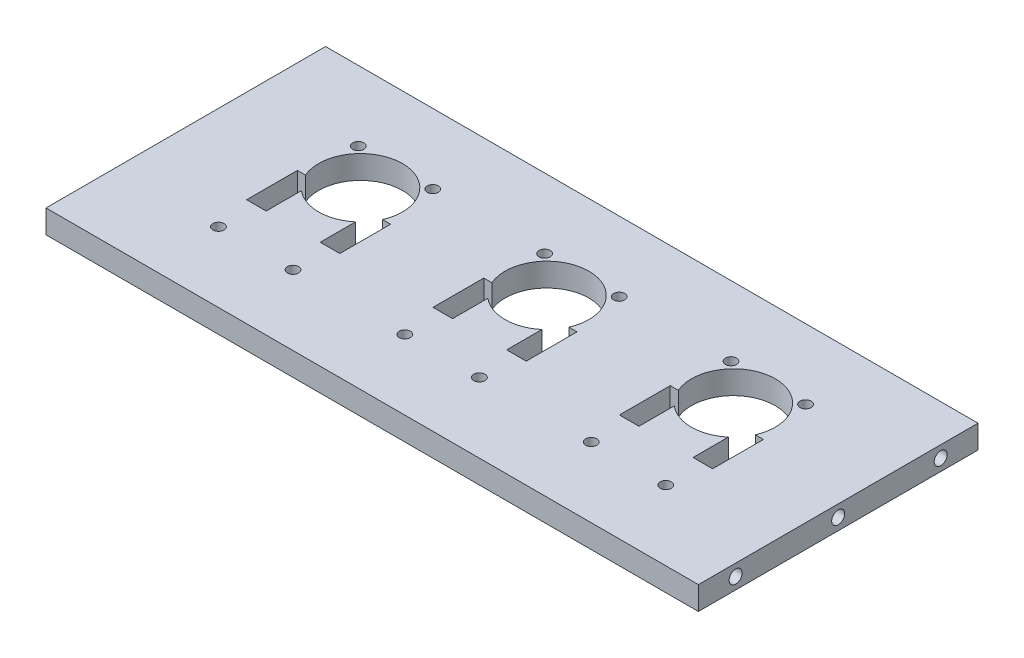
SolidWorks part; units mm, degrees
material "PET"
ref_plane "前视基准面" through (0, 0, 0) normal (0, 0, 1) x (1, 0, 0)
ref_plane "上视基准面" through (0, 0, 0) normal (0, 1, 0) x (1, 0, 0)
ref_plane "右视基准面" through (0, 0, 0) normal (1, 0, 0) x (0, 0, -1)
sketch "草图1" plane through (0, 0, 0) normal (0, 1, 0) x (1, 0, 0)
  line L0 (0, 0) -> (140, 0)
  line L1 (140, 0) -> (140, -60)
  line L2 (140, -60) -> (0, -60)
  line L3 (0, -60) -> (0, 0)
  dimension "D1" = 140
  dimension "D2" = 60
extrude "凸台-拉伸1" add sketch "草图1" along normal blind 5
ref_plane "基准面1" through (0, 0, 30) normal (0, 0, 1) x (1, 0, 0)
sketch "草图2" plane through (0, 5, 0) normal (0, 1, 0) x (1, 0, 0)
  line L0 (140, -30) -> (140, -13) construction
  line L1 (140, -60) -> (140, 0) construction
  line L2 (140, -30) -> (140, -47) construction
  line L3 (0, -13) -> (30, -13) construction
  line L4 (0, 0) -> (0, -60) construction
  line L5 (0, -13) -> (0, -47) construction
  line L6 (0, -47) -> (140, -47) construction
  line L7 (100, -13) -> (120, -13) construction
  line L8 (100, -13) -> (100, -47) construction
  line L9 (120, -13) -> (120, -47) construction
  line L10 (110, -13) -> (110, -15) construction
  line L11 (102, -15) -> (118, -15) construction
  line L12 (-2.75, -30) -> (2.75, -30) construction
  line L13 (100, -13) -> (140, -13) construction
  line L14 (100, -26.05) -> (100, -36.95)
  line L15 (100, -26.05) -> (101.7297, -26.05)
  line L16 (104.2, -29.3819) -> (104.2, -36.95)
  line L17 (104.2, -36.95) -> (100, -36.95)
  line L18 (120, -26.05) -> (118.2703, -26.05)
  line L19 (115.8, -29.3819) -> (115.8, -36.95)
  line L20 (115.8, -36.95) -> (120, -36.95)
  line L21 (120, -36.95) -> (120, -26.05)
  line L22 (110, -31.5) -> (110, -47) construction
  circle A0 centre (102, -15) radius 1.2
  circle A1 centre (118, -15) radius 1.2
  circle A2 centre (102, -45) radius 1.2
  circle A3 centre (118, -45) radius 1.2
  arc A4 (104.2, -29.3819) -> (115.8, -29.3819) centre (110, -22.5) ccw
  arc A5 (118.2703, -26.05) -> (101.7297, -26.05) centre (110, -22.5) ccw
  point P22 (110, -15)
  point P28 (110, -22.5)
  dimension "D12" = 2.4
  dimension "D13" = 2.4
  dimension "D15" = 13.05
  dimension "D1" = 17
  dimension "D2" = 17
  dimension "D3" = 140
  dimension "D4" = 13.05
  dimension "D5" = 10.9
  dimension "D6" = 20
  dimension "D7" = 20
  dimension "D10" = 16
  dimension "D11" = 15
  dimension "D14" = 9.5
  dimension "D16" = 23.95
  dimension "D17" = 10.9
extrude "电机孔位" cut sketch "草图2" against normal through all
ref_plane "基准面2" through (0, 2.5, 0) normal (0, 1, 0) x (1, 0, 0)
ref_axis "基准轴1" through (140, 5, 60) along (0, 0, -1)
ref_axis "基准轴2" through (140, 5, 60) along (0, -1, 0)
ref_point "点1"
sketch "草图4" plane through (0, 0, 0) normal (-1, 0, 0) x (0, 0, 1)
  line L0 (0, 5) -> (0, 0) construction
  line L1 (0, 2.5) -> (60, 2.5) construction
  line L2 (60, 5) -> (60, 0) construction
  line L3 (33, 2.5) -> (-33, 2.5) construction
  line L4 (60, 5) -> (60, 0) construction
  circle A0 centre (30, 2.5) radius 1.4
  circle A1 centre (8, 2.5) radius 1.4
  circle A2 centre (52, 2.5) radius 1.4
  dimension "D1" = 8
  dimension "D2" = 2.8
  dimension "D3" = 2.8
  dimension "D4" = 2.8
  dimension "D5" = 8
extrude "切除-拉伸3" cut sketch "草图4" against normal blind 5
ref_plane "基准面3" through (70, 0, 0) normal (1, 0, 0) x (0, 0, -1)
mirror "镜向1" about plane through (70, 0, 0) normal (1, 0, 0) of "切除-拉伸3"
pattern_linear "阵列(线性)1" count 3 spacing 40 along (-1, 0, 0) of "电机孔位"
sketch "草图6" plane through (0, 0, 0) normal (0, -1, 0) x (1, 0, 0)
  circle A0 centre (22, 45) radius 2
  circle A1 centre (38, 45) radius 2
  circle A2 centre (62, 45) radius 2
  circle A3 centre (78, 45) radius 2
  circle A4 centre (102, 45) radius 2
  circle A5 centre (118, 45) radius 2
extrude "切除-拉伸4" cut sketch "草图6" against normal blind 1
